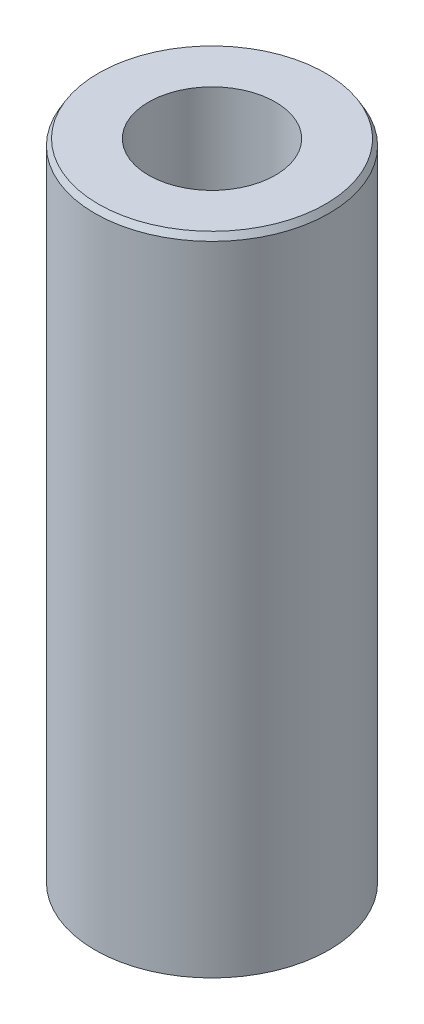
SolidWorks part; units mm, degrees
ref_plane "Front Plane" through (0, 0, 0) normal (0, 0, 1) x (1, 0, 0)
ref_plane "Top Plane" through (0, 0, 0) normal (0, 1, 0) x (1, 0, 0)
ref_plane "Right Plane" through (0, 0, 0) normal (1, 0, 0) x (0, 0, -1)
sketch "Sketch1" plane through (0, 0, 0) normal (0, 1, 0) x (1, 0, 0)
  circle A0 centre (0, 0) radius 52.5
  dimension "SHAFT_OD" = 105
extrude "Boss-Extrude1" add sketch "Sketch1" along normal blind 290.3634
sketch "Sketch2" plane through (0, 0, 0) normal (0, 1, 0) x (1, 0, 0)
  circle A0 centre (0, 0) radius 28.4374
  dimension "BORE_D" = 56.8749
extrude "Cut-Extrude1" cut sketch "Sketch2" along normal through all
chamfer "Chamfer1" distance 2.7894 angle 30 2 edges at (0, 290.3634, 52.5) (0, 0, 52.5) first distance on face at (0, 290.3634, 52.5) first distance on face at (0, 0, 28.4374)
